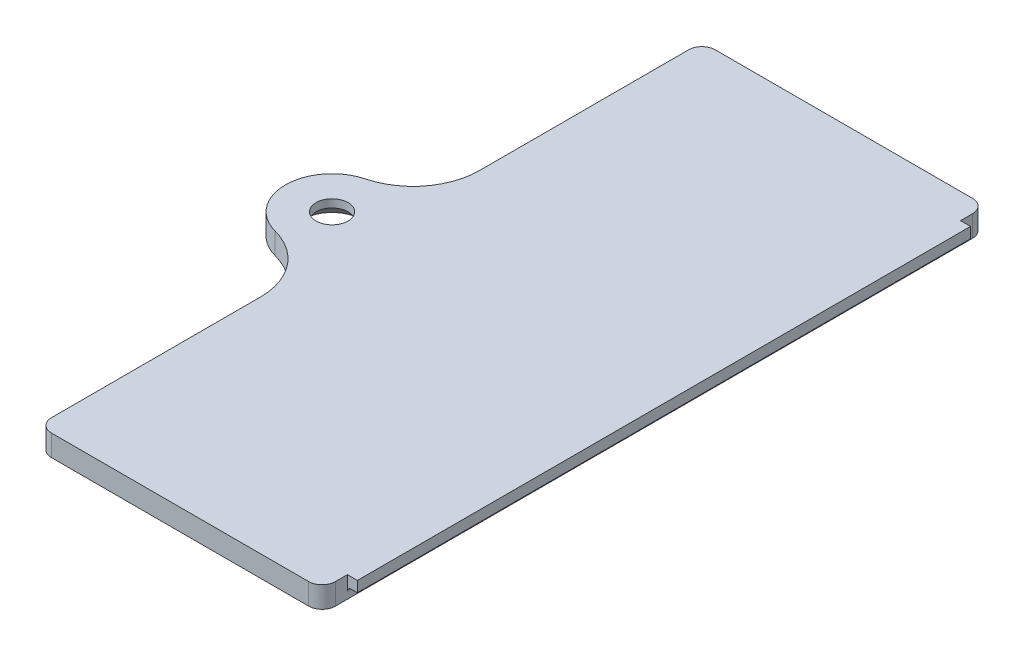
SolidWorks part; units mm, degrees
ref_plane "Front Plane" through (0, 0, 0) normal (0, 0, 1) x (1, 0, 0)
ref_plane "Top Plane" through (0, 0, 0) normal (0, 1, 0) x (1, 0, 0)
ref_plane "Right Plane" through (0, 0, 0) normal (1, 0, 0) x (0, 0, -1)
sketch "Door Plate 1.6 + screw ear (R5 / R3.5) Sketch" plane through (0, 0, 0) normal (0, 1, 0) x (1, 0, 0)
  line L0 (9.35, 15.1) -> (30.65, 15.1)
  line L1 (30.65, 15.1) -> (30.65, 64.9)
  line L2 (30.65, 64.9) -> (9.35, 64.9)
  line L3 (9.35, 64.9) -> (9.35, 48.2236)
  line L4 (9.35, 31.7764) -> (9.35, 15.1)
  arc A0 (9.35, 31.7764) -> (5.6147, 36.6138) centre (4.35, 31.7764) ccw
  arc A1 (5.6147, 36.6138) -> (5.6147, 43.3862) centre (6.5, 40) cw
  arc A2 (5.6147, 43.3862) -> (9.35, 48.2236) centre (4.35, 48.2236) ccw
extrude "Door Plate 1.6 + screw ear (R5 / R3.5)" add sketch "Door Plate 1.6 + screw ear (R5 / R3.5) Sketch" along normal blind 1.6
ref_plane "Hook Flange Plane y0.8" through (0, 0.8, 0) normal (0, 1, 0) x (1, 0, 0)
sketch "Hook Flange 0.75 x 0.8 (inner-face plane) Sketch" plane through (0, 0.8, 0) normal (0, 1, 0) x (1, 0, 0)
  line L0 (30.5, 17) -> (31.4, 17)
  line L1 (31.4, 17) -> (31.4, 63)
  line L2 (31.4, 63) -> (30.5, 63)
  line L3 (30.5, 63) -> (30.5, 17)
extrude "Hook Flange 0.75 x 0.8 (inner-face plane)" add sketch "Hook Flange 0.75 x 0.8 (inner-face plane) Sketch" along normal blind 0.8
sketch "Screw Hole 2.4 (free) Sketch" plane through (0, 0, 0) normal (0, 1, 0) x (1, 0, 0)
  circle A0 centre (6.5, 40) radius 1.2
extrude "Screw Hole 2.4 (free)" cut sketch "Screw Hole 2.4 (free) Sketch" along normal through all
chamfer "Screw CSK 90deg (M2)" distance 1 angle 45 1 edges at (6.5, 0, -38.8)
fillet "Door Corners R1 (print)" radius 1 4 edges at (9.35, 0.8, -64.9) (30.65, 0.8, -64.9) (30.65, 0.8, -15.1) (9.35, 0.8, -15.1)
fillet "Hook Flange Root Fillet R0.3" radius 0.3 1 edges at (30.65, 0.8, -40)
sketch "Door Text Slits 8160749347 + PLEASE RETURN (outer face, 0.84 stroke) Sketch" plane through (0, 0, 0) normal (0, 1, 0) x (1, 0, 0)
  line L0 (27.28, 17.22) -> (21.12, 17.22)
  line L1 (20.6, 17.74) -> (20.6, 20.5)
  line L2 (21.12, 21.02) -> (27.28, 21.02)
  line L3 (27.8, 20.5) -> (27.8, 17.74)
  line L4 (21.12, 17.32) -> (27.28, 17.32)
  line L5 (27.7, 17.74) -> (27.7, 20.5)
  line L6 (27.28, 20.92) -> (21.12, 20.92)
  line L7 (20.7, 20.5) -> (20.7, 17.74)
  line L8 (21.12, 24.28) -> (27.28, 24.28)
  line L9 (27.8, 23.76) -> (27.8, 22.76)
  line L10 (26.76, 22.76) -> (26.76, 23.24)
  line L11 (26.76, 23.24) -> (21.12, 23.24)
  line L12 (27.7, 23.76) -> (27.7, 22.76)
  line L13 (26.86, 22.76) -> (26.86, 23.34)
  line L14 (26.86, 23.34) -> (21.12, 23.34)
  line L15 (21.12, 24.18) -> (27.28, 24.18)
  line L16 (21.12, 30.3) -> (24.2, 30.3)
  line L17 (24.72, 29.78) -> (24.72, 27.54)
  line L18 (24.72, 27.54) -> (26.76, 27.54)
  line L19 (26.76, 27.54) -> (26.76, 29.78)
  line L20 (27.8, 29.78) -> (27.8, 27.02)
  line L21 (27.28, 26.5) -> (21.12, 26.5)
  line L22 (20.6, 27.02) -> (20.6, 29.78)
  line L23 (27.7, 29.78) -> (27.7, 27.02)
  line L24 (27.28, 26.6) -> (21.12, 26.6)
  line L25 (20.7, 27.02) -> (20.7, 29.78)
  line L26 (21.12, 30.2) -> (24.2, 30.2)
  line L27 (24.62, 29.78) -> (24.62, 27.44)
  line L28 (24.62, 27.44) -> (26.86, 27.44)
  line L29 (26.86, 27.44) -> (26.86, 29.78)
  line L30 (27.28, 31.14) -> (21.12, 31.14)
  line L31 (20.6, 31.66) -> (20.6, 34.42)
  line L32 (21.12, 34.94) -> (27.28, 34.94)
  line L33 (27.8, 34.42) -> (27.8, 31.66)
  line L34 (21.12, 31.24) -> (27.28, 31.24)
  line L35 (27.7, 31.66) -> (27.7, 34.42)
  line L36 (27.28, 34.84) -> (21.12, 34.84)
  line L37 (20.7, 34.42) -> (20.7, 31.66)
  line L38 (20.9832, 37.8817) -> (27.1432, 39.5617)
  line L39 (27.8, 39.06) -> (27.8, 36.3)
  line L40 (26.76, 36.3) -> (26.76, 38.3792)
  line L41 (26.76, 38.3792) -> (21.2568, 36.8783)
  line L42 (27.7, 39.06) -> (27.7, 36.3)
  line L43 (26.86, 36.3) -> (26.86, 38.5101)
  line L44 (26.86, 38.5101) -> (21.2305, 36.9748)
  line L45 (21.0095, 37.7852) -> (27.1695, 39.4652)
  line L46 (21.12, 44.22) -> (27.28, 44.22)
  line L47 (27.28, 43.18) -> (24.72, 43.18)
  line L48 (24.72, 43.18) -> (24.72, 41.46)
  line L49 (24.72, 41.46) -> (27.28, 41.46)
  line L50 (27.28, 40.42) -> (24.2, 40.42)
  line L51 (23.68, 40.94) -> (23.68, 43.18)
  line L52 (23.68, 43.18) -> (21.12, 43.18)
  line L53 (27.28, 40.52) -> (24.2, 40.52)
  line L54 (23.78, 40.94) -> (23.78, 43.28)
  line L55 (23.78, 43.28) -> (21.12, 43.28)
  line L56 (21.12, 44.12) -> (27.28, 44.12)
  line L57 (27.28, 43.28) -> (24.62, 43.28)
  line L58 (24.62, 43.28) -> (24.62, 41.36)
  line L59 (24.62, 41.36) -> (27.28, 41.36)
  line L60 (23.68, 47.82) -> (21.64, 47.82)
  line L61 (21.64, 47.82) -> (21.64, 45.58)
  line L62 (20.6, 45.58) -> (20.6, 48.34)
  line L63 (21.12, 48.86) -> (27.28, 48.86)
  line L64 (27.8, 48.34) -> (27.8, 45.58)
  line L65 (27.28, 45.06) -> (24.2, 45.06)
  line L66 (23.68, 45.58) -> (23.68, 47.82)
  line L67 (20.7, 48.34) -> (20.7, 45.58)
  line L68 (21.54, 45.58) -> (21.54, 47.92)
  line L69 (21.54, 47.92) -> (23.78, 47.92)
  line L70 (23.78, 47.92) -> (23.78, 45.58)
  line L71 (24.2, 45.16) -> (27.28, 45.16)
  line L72 (27.7, 45.58) -> (27.7, 48.34)
  line L73 (27.28, 48.76) -> (21.12, 48.76)
  line L74 (21.64, 52.46) -> (21.64, 50.22)
  line L75 (20.6, 50.22) -> (20.6, 52.98)
  line L76 (21.12, 53.5) -> (27.28, 53.5)
  line L77 (27.8, 52.98) -> (27.8, 50.22)
  line L78 (26.76, 50.22) -> (26.76, 52.46)
  line L79 (26.76, 52.46) -> (24.72, 52.46)
  line L80 (24.72, 52.46) -> (24.72, 51.02)
  line L81 (23.68, 51.02) -> (23.68, 52.46)
  line L82 (23.68, 52.46) -> (21.64, 52.46)
  line L83 (27.28, 53.4) -> (21.12, 53.4)
  line L84 (20.7, 52.98) -> (20.7, 50.22)
  line L85 (21.54, 50.22) -> (21.54, 52.56)
  line L86 (21.54, 52.56) -> (23.78, 52.56)
  line L87 (23.78, 52.56) -> (23.78, 51.02)
  line L88 (24.62, 51.02) -> (24.62, 52.56)
  line L89 (24.62, 52.56) -> (26.86, 52.56)
  line L90 (26.86, 52.56) -> (26.86, 50.22)
  line L91 (27.7, 50.22) -> (27.7, 52.98)
  line L92 (21.12, 58.14) -> (27.28, 58.14)
  line L93 (27.28, 57.1) -> (24.72, 57.1)
  line L94 (24.72, 57.1) -> (24.72, 55.38)
  line L95 (24.72, 55.38) -> (27.28, 55.38)
  line L96 (27.28, 54.34) -> (24.2, 54.34)
  line L97 (23.68, 54.86) -> (23.68, 57.1)
  line L98 (23.68, 57.1) -> (21.12, 57.1)
  line L99 (27.28, 54.44) -> (24.2, 54.44)
  line L100 (23.78, 54.86) -> (23.78, 57.2)
  line L101 (23.78, 57.2) -> (21.12, 57.2)
  line L102 (21.12, 58.04) -> (27.28, 58.04)
  line L103 (27.28, 57.2) -> (24.62, 57.2)
  line L104 (24.62, 57.2) -> (24.62, 55.28)
  line L105 (24.62, 55.28) -> (27.28, 55.28)
  line L106 (20.9832, 61.0817) -> (27.1432, 62.7617)
  line L107 (27.8, 62.26) -> (27.8, 59.5)
  line L108 (26.76, 59.5) -> (26.76, 61.5792)
  line L109 (26.76, 61.5792) -> (21.2568, 60.0783)
  line L110 (27.7, 62.26) -> (27.7, 59.5)
  line L111 (26.86, 59.5) -> (26.86, 61.7101)
  line L112 (26.86, 61.7101) -> (21.2305, 60.1748)
  line L113 (21.0095, 60.9852) -> (27.1695, 62.6652)
  line L114 (18.28, 19.76) -> (16.2, 19.76)
  line L115 (15.68, 19.24) -> (15.68, 17.8)
  line L116 (15.68, 17.8) -> (14.12, 17.8)
  line L117 (14.12, 16.76) -> (18.28, 16.76)
  line L118 (18.8, 17.28) -> (18.8, 19.24)
  line L119 (14.12, 16.86) -> (18.28, 16.86)
  line L120 (18.7, 17.28) -> (18.7, 19.24)
  line L121 (18.28, 19.66) -> (16.2, 19.66)
  line L122 (15.78, 19.24) -> (15.78, 17.7)
  line L123 (15.78, 17.7) -> (14.12, 17.7)
  line L124 (13.6, 21.12) -> (13.6, 22.48)
  line L125 (14.64, 22.48) -> (14.64, 21.64)
  line L126 (14.64, 21.64) -> (18.28, 21.64)
  line L127 (18.28, 20.6) -> (14.12, 20.6)
  line L128 (14.54, 21.54) -> (18.28, 21.54)
  line L129 (18.28, 20.7) -> (14.12, 20.7)
  line L130 (13.7, 21.12) -> (13.7, 22.48)
  line L131 (14.54, 22.48) -> (14.54, 21.54)
  line L132 (14.64, 25.72) -> (14.64, 24.88)
  line L133 (14.64, 24.88) -> (15.68, 24.88)
  line L134 (15.68, 24.88) -> (15.68, 25.42)
  line L135 (16.72, 25.42) -> (16.72, 24.88)
  line L136 (16.72, 24.88) -> (17.76, 24.88)
  line L137 (17.76, 24.88) -> (17.76, 25.72)
  line L138 (18.8, 25.72) -> (18.8, 24.36)
  line L139 (18.28, 23.84) -> (14.12, 23.84)
  line L140 (13.6, 24.36) -> (13.6, 25.72)
  line L141 (18.7, 25.72) -> (18.7, 24.36)
  line L142 (18.28, 23.94) -> (14.12, 23.94)
  line L143 (13.7, 24.36) -> (13.7, 25.72)
  line L144 (14.54, 25.72) -> (14.54, 24.78)
  line L145 (14.54, 24.78) -> (15.78, 24.78)
  line L146 (15.78, 24.78) -> (15.78, 25.42)
  line L147 (16.62, 25.42) -> (16.62, 24.78)
  line L148 (16.62, 24.78) -> (17.86, 24.78)
  line L149 (17.86, 24.78) -> (17.86, 25.72)
  line L150 (14.12, 29.04) -> (15.68, 29.04)
  line L151 (15.68, 29.04) -> (15.68, 28.12)
  line L152 (15.68, 28.12) -> (14.12, 28.12)
  line L153 (14.12, 27.08) -> (18.28, 27.08)
  line L154 (18.8, 27.6) -> (18.8, 29.56)
  line L155 (18.28, 30.08) -> (14.12, 30.08)
  line L156 (14.12, 27.18) -> (18.28, 27.18)
  line L157 (18.7, 27.6) -> (18.7, 29.56)
  line L158 (18.28, 29.98) -> (14.12, 29.98)
  line L159 (14.12, 29.14) -> (15.78, 29.14)
  line L160 (15.78, 29.14) -> (15.78, 28.02)
  line L161 (15.78, 28.02) -> (14.12, 28.02)
  line L162 (13.6, 31.44) -> (13.6, 33.2)
  line L163 (14.12, 33.72) -> (16.2, 33.72)
  line L164 (16.72, 33.2) -> (16.72, 31.96)
  line L165 (16.72, 31.96) -> (17.76, 31.96)
  line L166 (17.76, 31.96) -> (17.76, 33.2)
  line L167 (18.8, 33.2) -> (18.8, 31.44)
  line L168 (18.28, 30.92) -> (16.2, 30.92)
  line L169 (15.68, 31.44) -> (15.68, 32.68)
  line L170 (15.68, 32.68) -> (14.64, 32.68)
  line L171 (14.64, 32.68) -> (14.64, 31.44)
  line L172 (17.86, 31.86) -> (17.86, 33.2)
  line L173 (18.7, 33.2) -> (18.7, 31.44)
  line L174 (18.28, 31.02) -> (16.2, 31.02)
  line L175 (15.78, 31.44) -> (15.78, 32.78)
  line L176 (15.78, 32.78) -> (14.54, 32.78)
  line L177 (14.54, 32.78) -> (14.54, 31.44)
  line L178 (13.7, 31.44) -> (13.7, 33.2)
  line L179 (14.12, 33.62) -> (16.2, 33.62)
  line L180 (16.62, 33.2) -> (16.62, 31.86)
  line L181 (16.62, 31.86) -> (17.86, 31.86)
  line L182 (14.64, 36.44) -> (14.64, 35.6)
  line L183 (14.64, 35.6) -> (15.68, 35.6)
  line L184 (15.68, 35.6) -> (15.68, 36.14)
  line L185 (16.72, 36.14) -> (16.72, 35.6)
  line L186 (16.72, 35.6) -> (17.76, 35.6)
  line L187 (17.76, 35.6) -> (17.76, 36.44)
  line L188 (18.8, 36.44) -> (18.8, 35.08)
  line L189 (18.28, 34.56) -> (14.12, 34.56)
  line L190 (13.6, 35.08) -> (13.6, 36.44)
  line L191 (18.7, 36.44) -> (18.7, 35.08)
  line L192 (18.28, 34.66) -> (14.12, 34.66)
  line L193 (13.7, 35.08) -> (13.7, 36.44)
  line L194 (14.54, 36.44) -> (14.54, 35.5)
  line L195 (14.54, 35.5) -> (15.78, 35.5)
  line L196 (15.78, 35.5) -> (15.78, 36.14)
  line L197 (16.62, 36.14) -> (16.62, 35.5)
  line L198 (16.62, 35.5) -> (17.86, 35.5)
  line L199 (17.86, 35.5) -> (17.86, 36.44)
  line L200 (15.68, 43.52) -> (15.68, 43.4246)
  line L201 (15.68, 43.4246) -> (14.3226, 43.9989)
  line L202 (13.9174, 43.0411) -> (15.68, 42.2954)
  line L203 (15.68, 42.2954) -> (15.68, 41.28)
  line L204 (15.68, 41.28) -> (14.12, 41.28)
  line L205 (14.12, 40.24) -> (18.28, 40.24)
  line L206 (18.8, 40.76) -> (18.8, 43.52)
  line L207 (18.28, 44.04) -> (16.2, 44.04)
  line L208 (14.12, 40.34) -> (18.28, 40.34)
  line L209 (18.7, 40.76) -> (18.7, 43.52)
  line L210 (18.28, 43.94) -> (16.2, 43.94)
  line L211 (15.78, 43.52) -> (15.78, 43.2737)
  line L212 (15.78, 43.2737) -> (14.2836, 43.9068)
  line L213 (13.9564, 43.1332) -> (15.78, 42.3617)
  line L214 (15.78, 42.3617) -> (15.78, 41.18)
  line L215 (15.78, 41.18) -> (14.12, 41.18)
  line L216 (14.64, 46.76) -> (14.64, 45.92)
  line L217 (14.64, 45.92) -> (15.68, 45.92)
  line L218 (15.68, 45.92) -> (15.68, 46.46)
  line L219 (16.72, 46.46) -> (16.72, 45.92)
  line L220 (16.72, 45.92) -> (17.76, 45.92)
  line L221 (17.76, 45.92) -> (17.76, 46.76)
  line L222 (18.8, 46.76) -> (18.8, 45.4)
  line L223 (18.28, 44.88) -> (14.12, 44.88)
  line L224 (13.6, 45.4) -> (13.6, 46.76)
  line L225 (18.7, 46.76) -> (18.7, 45.4)
  line L226 (18.28, 44.98) -> (14.12, 44.98)
  line L227 (13.7, 45.4) -> (13.7, 46.76)
  line L228 (14.54, 46.76) -> (14.54, 45.82)
  line L229 (14.54, 45.82) -> (15.78, 45.82)
  line L230 (15.78, 45.82) -> (15.78, 46.46)
  line L231 (16.62, 46.46) -> (16.62, 45.82)
  line L232 (16.62, 45.82) -> (17.86, 45.82)
  line L233 (17.86, 45.82) -> (17.86, 46.76)
  line L234 (14.12, 49) -> (17.76, 49)
  line L235 (17.76, 49) -> (17.76, 48.64)
  line L236 (18.8, 48.64) -> (18.8, 50.4)
  line L237 (17.76, 50.4) -> (17.76, 50.04)
  line L238 (17.76, 50.04) -> (14.12, 50.04)
  line L239 (18.7, 48.64) -> (18.7, 50.4)
  line L240 (17.86, 50.4) -> (17.86, 49.94)
  line L241 (17.86, 49.94) -> (14.12, 49.94)
  line L242 (14.12, 49.1) -> (17.86, 49.1)
  line L243 (17.86, 49.1) -> (17.86, 48.64)
  line L244 (14.12, 54.76) -> (18.28, 54.76)
  line L245 (18.28, 53.72) -> (14.64, 53.72)
  line L246 (14.64, 53.72) -> (14.64, 52.8)
  line L247 (14.64, 52.8) -> (18.28, 52.8)
  line L248 (18.28, 51.76) -> (14.12, 51.76)
  line L249 (13.6, 52.28) -> (13.6, 54.24)
  line L250 (14.54, 52.7) -> (18.28, 52.7)
  line L251 (18.28, 51.86) -> (14.12, 51.86)
  line L252 (13.7, 52.28) -> (13.7, 54.24)
  line L253 (14.12, 54.66) -> (18.28, 54.66)
  line L254 (18.28, 53.82) -> (14.54, 53.82)
  line L255 (14.54, 53.82) -> (14.54, 52.7)
  line L256 (15.68, 58.88) -> (15.68, 58.7846)
  line L257 (15.68, 58.7846) -> (14.3226, 59.3589)
  line L258 (13.9174, 58.4011) -> (15.68, 57.6554)
  line L259 (15.68, 57.6554) -> (15.68, 56.64)
  line L260 (15.68, 56.64) -> (14.12, 56.64)
  line L261 (14.12, 55.6) -> (18.28, 55.6)
  line L262 (18.8, 56.12) -> (18.8, 58.88)
  line L263 (18.28, 59.4) -> (16.2, 59.4)
  line L264 (14.12, 55.7) -> (18.28, 55.7)
  line L265 (18.7, 56.12) -> (18.7, 58.88)
  line L266 (18.28, 59.3) -> (16.2, 59.3)
  line L267 (15.78, 58.88) -> (15.78, 58.6337)
  line L268 (15.78, 58.6337) -> (14.2836, 59.2668)
  line L269 (13.9564, 58.4932) -> (15.78, 57.7217)
  line L270 (15.78, 57.7217) -> (15.78, 56.54)
  line L271 (15.78, 56.54) -> (14.12, 56.54)
  line L272 (14.12, 63.24) -> (18.28, 63.24)
  line L273 (18.8, 62.72) -> (18.8, 60.76)
  line L274 (18.28, 60.24) -> (14.12, 60.24)
  line L275 (14.12, 61.28) -> (17.76, 61.28)
  line L276 (17.76, 61.28) -> (17.76, 62.2)
  line L277 (17.76, 62.2) -> (14.12, 62.2)
  line L278 (18.28, 60.34) -> (14.12, 60.34)
  line L279 (14.12, 61.18) -> (17.86, 61.18)
  line L280 (17.86, 61.18) -> (17.86, 62.3)
  line L281 (17.86, 62.3) -> (14.12, 62.3)
  line L282 (14.12, 63.14) -> (18.28, 63.14)
  line L283 (18.7, 62.72) -> (18.7, 60.76)
  arc A0 (27.8, 17.74) -> (27.28, 17.22) centre (27.28, 17.74) cw
  arc A1 (21.12, 17.22) -> (20.6, 17.74) centre (21.12, 17.74) cw
  arc A2 (20.6, 20.5) -> (21.12, 21.02) centre (21.12, 20.5) cw
  arc A3 (27.28, 21.02) -> (27.8, 20.5) centre (27.28, 20.5) cw
  arc A4 (20.7, 17.74) -> (21.12, 17.32) centre (21.12, 17.74) ccw
  arc A5 (27.28, 17.32) -> (27.7, 17.74) centre (27.28, 17.74) ccw
  arc A6 (27.7, 20.5) -> (27.28, 20.92) centre (27.28, 20.5) ccw
  arc A7 (21.12, 20.92) -> (20.7, 20.5) centre (21.12, 20.5) ccw
  arc A8 (21.12, 23.24) -> (21.12, 24.28) centre (21.12, 23.76) cw
  arc A9 (27.28, 24.28) -> (27.8, 23.76) centre (27.28, 23.76) cw
  arc A10 (27.8, 22.76) -> (26.76, 22.76) centre (27.28, 22.76) cw
  arc A11 (27.7, 22.76) -> (26.86, 22.76) centre (27.28, 22.76) cw
  arc A12 (21.12, 23.34) -> (21.12, 24.18) centre (21.12, 23.76) cw
  arc A13 (27.28, 24.18) -> (27.7, 23.76) centre (27.28, 23.76) cw
  arc A14 (20.6, 29.78) -> (21.12, 30.3) centre (21.12, 29.78) cw
  arc A15 (24.2, 30.3) -> (24.72, 29.78) centre (24.2, 29.78) cw
  arc A16 (26.76, 29.78) -> (27.8, 29.78) centre (27.28, 29.78) cw
  arc A17 (27.8, 27.02) -> (27.28, 26.5) centre (27.28, 27.02) cw
  arc A18 (21.12, 26.5) -> (20.6, 27.02) centre (21.12, 27.02) cw
  arc A19 (26.86, 29.78) -> (27.7, 29.78) centre (27.28, 29.78) cw
  arc A20 (27.7, 27.02) -> (27.28, 26.6) centre (27.28, 27.02) cw
  arc A21 (21.12, 26.6) -> (20.7, 27.02) centre (21.12, 27.02) cw
  arc A22 (20.7, 29.78) -> (21.12, 30.2) centre (21.12, 29.78) cw
  arc A23 (24.2, 30.2) -> (24.62, 29.78) centre (24.2, 29.78) cw
  arc A24 (27.8, 31.66) -> (27.28, 31.14) centre (27.28, 31.66) cw
  arc A25 (21.12, 31.14) -> (20.6, 31.66) centre (21.12, 31.66) cw
  arc A26 (20.6, 34.42) -> (21.12, 34.94) centre (21.12, 34.42) cw
  arc A27 (27.28, 34.94) -> (27.8, 34.42) centre (27.28, 34.42) cw
  arc A28 (20.7, 31.66) -> (21.12, 31.24) centre (21.12, 31.66) ccw
  arc A29 (27.28, 31.24) -> (27.7, 31.66) centre (27.28, 31.66) ccw
  arc A30 (27.7, 34.42) -> (27.28, 34.84) centre (27.28, 34.42) ccw
  arc A31 (21.12, 34.84) -> (20.7, 34.42) centre (21.12, 34.42) ccw
  arc A32 (21.2568, 36.8783) -> (20.9832, 37.8817) centre (21.12, 37.38) cw
  arc A33 (27.1432, 39.5617) -> (27.8, 39.06) centre (27.28, 39.06) cw
  arc A34 (27.8, 36.3) -> (26.76, 36.3) centre (27.28, 36.3) cw
  arc A35 (27.7, 36.3) -> (26.86, 36.3) centre (27.28, 36.3) cw
  arc A36 (21.2305, 36.9748) -> (21.0095, 37.7852) centre (21.12, 37.38) cw
  arc A37 (27.1695, 39.4652) -> (27.7, 39.06) centre (27.28, 39.06) cw
  arc A38 (21.12, 43.18) -> (21.12, 44.22) centre (21.12, 43.7) cw
  arc A39 (27.28, 44.22) -> (27.8, 43.7) centre (27.28, 43.7) cw
  arc A40 (27.8, 43.7) -> (27.28, 43.18) centre (27.28, 43.7) cw
  arc A41 (27.28, 41.46) -> (27.8, 40.94) centre (27.28, 40.94) cw
  arc A42 (27.8, 40.94) -> (27.28, 40.42) centre (27.28, 40.94) cw
  arc A43 (24.2, 40.42) -> (23.68, 40.94) centre (24.2, 40.94) cw
  arc A44 (27.28, 41.36) -> (27.7, 40.94) centre (27.28, 40.94) cw
  arc A45 (27.7, 40.94) -> (27.28, 40.52) centre (27.28, 40.94) cw
  arc A46 (24.2, 40.52) -> (23.78, 40.94) centre (24.2, 40.94) cw
  arc A47 (21.12, 43.28) -> (21.12, 44.12) centre (21.12, 43.7) cw
  arc A48 (27.28, 44.12) -> (27.7, 43.7) centre (27.28, 43.7) cw
  arc A49 (27.7, 43.7) -> (27.28, 43.28) centre (27.28, 43.7) cw
  arc A50 (21.64, 45.58) -> (20.6, 45.58) centre (21.12, 45.58) cw
  arc A51 (20.6, 48.34) -> (21.12, 48.86) centre (21.12, 48.34) cw
  arc A52 (27.28, 48.86) -> (27.8, 48.34) centre (27.28, 48.34) cw
  arc A53 (27.8, 45.58) -> (27.28, 45.06) centre (27.28, 45.58) cw
  arc A54 (24.2, 45.06) -> (23.68, 45.58) centre (24.2, 45.58) cw
  arc A55 (21.12, 48.76) -> (20.7, 48.34) centre (21.12, 48.34) ccw
  arc A56 (20.7, 45.58) -> (21.54, 45.58) centre (21.12, 45.58) ccw
  arc A57 (23.78, 45.58) -> (24.2, 45.16) centre (24.2, 45.58) ccw
  arc A58 (27.28, 45.16) -> (27.7, 45.58) centre (27.28, 45.58) ccw
  arc A59 (27.7, 48.34) -> (27.28, 48.76) centre (27.28, 48.34) ccw
  arc A60 (21.64, 50.22) -> (20.6, 50.22) centre (21.12, 50.22) cw
  arc A61 (20.6, 52.98) -> (21.12, 53.5) centre (21.12, 52.98) cw
  arc A62 (27.28, 53.5) -> (27.8, 52.98) centre (27.28, 52.98) cw
  arc A63 (27.8, 50.22) -> (26.76, 50.22) centre (27.28, 50.22) cw
  arc A64 (24.72, 51.02) -> (23.68, 51.02) centre (24.2, 51.02) cw
  arc A65 (27.7, 52.98) -> (27.28, 53.4) centre (27.28, 52.98) ccw
  arc A66 (21.12, 53.4) -> (20.7, 52.98) centre (21.12, 52.98) ccw
  arc A67 (20.7, 50.22) -> (21.54, 50.22) centre (21.12, 50.22) ccw
  arc A68 (23.78, 51.02) -> (24.62, 51.02) centre (24.2, 51.02) ccw
  arc A69 (26.86, 50.22) -> (27.7, 50.22) centre (27.28, 50.22) ccw
  arc A70 (21.12, 57.1) -> (21.12, 58.14) centre (21.12, 57.62) cw
  arc A71 (27.28, 58.14) -> (27.8, 57.62) centre (27.28, 57.62) cw
  arc A72 (27.8, 57.62) -> (27.28, 57.1) centre (27.28, 57.62) cw
  arc A73 (27.28, 55.38) -> (27.8, 54.86) centre (27.28, 54.86) cw
  arc A74 (27.8, 54.86) -> (27.28, 54.34) centre (27.28, 54.86) cw
  arc A75 (24.2, 54.34) -> (23.68, 54.86) centre (24.2, 54.86) cw
  arc A76 (27.28, 55.28) -> (27.7, 54.86) centre (27.28, 54.86) cw
  arc A77 (27.7, 54.86) -> (27.28, 54.44) centre (27.28, 54.86) cw
  arc A78 (24.2, 54.44) -> (23.78, 54.86) centre (24.2, 54.86) cw
  arc A79 (21.12, 57.2) -> (21.12, 58.04) centre (21.12, 57.62) cw
  arc A80 (27.28, 58.04) -> (27.7, 57.62) centre (27.28, 57.62) cw
  arc A81 (27.7, 57.62) -> (27.28, 57.2) centre (27.28, 57.62) cw
  arc A82 (21.2568, 60.0783) -> (20.9832, 61.0817) centre (21.12, 60.58) cw
  arc A83 (27.1432, 62.7617) -> (27.8, 62.26) centre (27.28, 62.26) cw
  arc A84 (27.8, 59.5) -> (26.76, 59.5) centre (27.28, 59.5) cw
  arc A85 (27.7, 59.5) -> (26.86, 59.5) centre (27.28, 59.5) cw
  arc A86 (21.2305, 60.1748) -> (21.0095, 60.9852) centre (21.12, 60.58) cw
  arc A87 (27.1695, 62.6652) -> (27.7, 62.26) centre (27.28, 62.26) cw
  arc A88 (16.2, 19.76) -> (15.68, 19.24) centre (16.2, 19.24) ccw
  arc A89 (14.12, 17.8) -> (14.12, 16.76) centre (14.12, 17.28) ccw
  arc A90 (18.28, 16.76) -> (18.8, 17.28) centre (18.28, 17.28) ccw
  arc A91 (18.8, 19.24) -> (18.28, 19.76) centre (18.28, 19.24) ccw
  arc A92 (14.12, 17.7) -> (14.12, 16.86) centre (14.12, 17.28) ccw
  arc A93 (18.28, 16.86) -> (18.7, 17.28) centre (18.28, 17.28) ccw
  arc A94 (18.7, 19.24) -> (18.28, 19.66) centre (18.28, 19.24) ccw
  arc A95 (16.2, 19.66) -> (15.78, 19.24) centre (16.2, 19.24) ccw
  arc A96 (13.6, 22.48) -> (14.64, 22.48) centre (14.12, 22.48) cw
  arc A97 (18.28, 21.64) -> (18.8, 21.12) centre (18.28, 21.12) cw
  arc A98 (18.8, 21.12) -> (18.28, 20.6) centre (18.28, 21.12) cw
  arc A99 (14.12, 20.6) -> (13.6, 21.12) centre (14.12, 21.12) cw
  arc A100 (18.28, 21.54) -> (18.7, 21.12) centre (18.28, 21.12) cw
  arc A101 (18.7, 21.12) -> (18.28, 20.7) centre (18.28, 21.12) cw
  arc A102 (14.12, 20.7) -> (13.7, 21.12) centre (14.12, 21.12) cw
  arc A103 (13.7, 22.48) -> (14.54, 22.48) centre (14.12, 22.48) cw
  arc A104 (15.68, 25.42) -> (16.72, 25.42) centre (16.2, 25.42) cw
  arc A105 (17.76, 25.72) -> (18.8, 25.72) centre (18.28, 25.72) cw
  arc A106 (18.8, 24.36) -> (18.28, 23.84) centre (18.28, 24.36) cw
  arc A107 (14.12, 23.84) -> (13.6, 24.36) centre (14.12, 24.36) cw
  arc A108 (13.6, 25.72) -> (14.64, 25.72) centre (14.12, 25.72) cw
  arc A109 (17.86, 25.72) -> (18.7, 25.72) centre (18.28, 25.72) cw
  arc A110 (18.7, 24.36) -> (18.28, 23.94) centre (18.28, 24.36) cw
  arc A111 (14.12, 23.94) -> (13.7, 24.36) centre (14.12, 24.36) cw
  arc A112 (13.7, 25.72) -> (14.54, 25.72) centre (14.12, 25.72) cw
  arc A113 (15.78, 25.42) -> (16.62, 25.42) centre (16.2, 25.42) cw
  arc A114 (14.12, 30.08) -> (14.12, 29.04) centre (14.12, 29.56) ccw
  arc A115 (14.12, 28.12) -> (14.12, 27.08) centre (14.12, 27.6) ccw
  arc A116 (18.28, 27.08) -> (18.8, 27.6) centre (18.28, 27.6) ccw
  arc A117 (18.8, 29.56) -> (18.28, 30.08) centre (18.28, 29.56) ccw
  arc A118 (14.12, 28.02) -> (14.12, 27.18) centre (14.12, 27.6) ccw
  arc A119 (18.28, 27.18) -> (18.7, 27.6) centre (18.28, 27.6) ccw
  arc A120 (18.7, 29.56) -> (18.28, 29.98) centre (18.28, 29.56) ccw
  arc A121 (14.12, 29.98) -> (14.12, 29.14) centre (14.12, 29.56) ccw
  arc A122 (14.64, 31.44) -> (13.6, 31.44) centre (14.12, 31.44) cw
  arc A123 (13.6, 33.2) -> (14.12, 33.72) centre (14.12, 33.2) cw
  arc A124 (16.2, 33.72) -> (16.72, 33.2) centre (16.2, 33.2) cw
  arc A125 (17.76, 33.2) -> (18.8, 33.2) centre (18.28, 33.2) cw
  arc A126 (18.8, 31.44) -> (18.28, 30.92) centre (18.28, 31.44) cw
  arc A127 (16.2, 30.92) -> (15.68, 31.44) centre (16.2, 31.44) cw
  arc A128 (17.86, 33.2) -> (18.7, 33.2) centre (18.28, 33.2) cw
  arc A129 (18.7, 31.44) -> (18.28, 31.02) centre (18.28, 31.44) cw
  arc A130 (16.2, 31.02) -> (15.78, 31.44) centre (16.2, 31.44) cw
  arc A131 (14.54, 31.44) -> (13.7, 31.44) centre (14.12, 31.44) cw
  arc A132 (13.7, 33.2) -> (14.12, 33.62) centre (14.12, 33.2) cw
  arc A133 (16.2, 33.62) -> (16.62, 33.2) centre (16.2, 33.2) cw
  arc A134 (15.68, 36.14) -> (16.72, 36.14) centre (16.2, 36.14) cw
  arc A135 (17.76, 36.44) -> (18.8, 36.44) centre (18.28, 36.44) cw
  arc A136 (18.8, 35.08) -> (18.28, 34.56) centre (18.28, 35.08) cw
  arc A137 (14.12, 34.56) -> (13.6, 35.08) centre (14.12, 35.08) cw
  arc A138 (13.6, 36.44) -> (14.64, 36.44) centre (14.12, 36.44) cw
  arc A139 (17.86, 36.44) -> (18.7, 36.44) centre (18.28, 36.44) cw
  arc A140 (18.7, 35.08) -> (18.28, 34.66) centre (18.28, 35.08) cw
  arc A141 (14.12, 34.66) -> (13.7, 35.08) centre (14.12, 35.08) cw
  arc A142 (13.7, 36.44) -> (14.54, 36.44) centre (14.12, 36.44) cw
  arc A143 (15.78, 36.14) -> (16.62, 36.14) centre (16.2, 36.14) cw
  arc A144 (14.3226, 43.9989) -> (13.9174, 43.0411) centre (14.12, 43.52) ccw
  arc A145 (14.12, 41.28) -> (14.12, 40.24) centre (14.12, 40.76) ccw
  arc A146 (18.28, 40.24) -> (18.8, 40.76) centre (18.28, 40.76) ccw
  arc A147 (18.8, 43.52) -> (18.28, 44.04) centre (18.28, 43.52) ccw
  arc A148 (16.2, 44.04) -> (15.68, 43.52) centre (16.2, 43.52) ccw
  arc A149 (14.12, 41.18) -> (14.12, 40.34) centre (14.12, 40.76) ccw
  arc A150 (18.28, 40.34) -> (18.7, 40.76) centre (18.28, 40.76) ccw
  arc A151 (18.7, 43.52) -> (18.28, 43.94) centre (18.28, 43.52) ccw
  arc A152 (16.2, 43.94) -> (15.78, 43.52) centre (16.2, 43.52) ccw
  arc A153 (14.2836, 43.9068) -> (13.9564, 43.1332) centre (14.12, 43.52) ccw
  arc A154 (15.68, 46.46) -> (16.72, 46.46) centre (16.2, 46.46) cw
  arc A155 (17.76, 46.76) -> (18.8, 46.76) centre (18.28, 46.76) cw
  arc A156 (18.8, 45.4) -> (18.28, 44.88) centre (18.28, 45.4) cw
  arc A157 (14.12, 44.88) -> (13.6, 45.4) centre (14.12, 45.4) cw
  arc A158 (13.6, 46.76) -> (14.64, 46.76) centre (14.12, 46.76) cw
  arc A159 (17.86, 46.76) -> (18.7, 46.76) centre (18.28, 46.76) cw
  arc A160 (18.7, 45.4) -> (18.28, 44.98) centre (18.28, 45.4) cw
  arc A161 (14.12, 44.98) -> (13.7, 45.4) centre (14.12, 45.4) cw
  arc A162 (13.7, 46.76) -> (14.54, 46.76) centre (14.12, 46.76) cw
  arc A163 (15.78, 46.46) -> (16.62, 46.46) centre (16.2, 46.46) cw
  arc A164 (14.12, 50.04) -> (14.12, 49) centre (14.12, 49.52) ccw
  arc A165 (17.76, 48.64) -> (18.8, 48.64) centre (18.28, 48.64) ccw
  arc A166 (18.8, 50.4) -> (17.76, 50.4) centre (18.28, 50.4) ccw
  arc A167 (17.86, 48.64) -> (18.7, 48.64) centre (18.28, 48.64) ccw
  arc A168 (18.7, 50.4) -> (17.86, 50.4) centre (18.28, 50.4) ccw
  arc A169 (14.12, 49.94) -> (14.12, 49.1) centre (14.12, 49.52) ccw
  arc A170 (18.28, 54.76) -> (18.8, 54.24) centre (18.28, 54.24) cw
  arc A171 (18.8, 54.24) -> (18.28, 53.72) centre (18.28, 54.24) cw
  arc A172 (18.28, 52.8) -> (18.8, 52.28) centre (18.28, 52.28) cw
  arc A173 (18.8, 52.28) -> (18.28, 51.76) centre (18.28, 52.28) cw
  arc A174 (14.12, 51.76) -> (13.6, 52.28) centre (14.12, 52.28) cw
  arc A175 (13.6, 54.24) -> (14.12, 54.76) centre (14.12, 54.24) cw
  arc A176 (18.28, 52.7) -> (18.7, 52.28) centre (18.28, 52.28) cw
  arc A177 (18.7, 52.28) -> (18.28, 51.86) centre (18.28, 52.28) cw
  arc A178 (14.12, 51.86) -> (13.7, 52.28) centre (14.12, 52.28) cw
  arc A179 (13.7, 54.24) -> (14.12, 54.66) centre (14.12, 54.24) cw
  arc A180 (18.28, 54.66) -> (18.7, 54.24) centre (18.28, 54.24) cw
  arc A181 (18.7, 54.24) -> (18.28, 53.82) centre (18.28, 54.24) cw
  arc A182 (14.3226, 59.3589) -> (13.9174, 58.4011) centre (14.12, 58.88) ccw
  arc A183 (14.12, 56.64) -> (14.12, 55.6) centre (14.12, 56.12) ccw
  arc A184 (18.28, 55.6) -> (18.8, 56.12) centre (18.28, 56.12) ccw
  arc A185 (18.8, 58.88) -> (18.28, 59.4) centre (18.28, 58.88) ccw
  arc A186 (16.2, 59.4) -> (15.68, 58.88) centre (16.2, 58.88) ccw
  arc A187 (14.12, 56.54) -> (14.12, 55.7) centre (14.12, 56.12) ccw
  arc A188 (18.28, 55.7) -> (18.7, 56.12) centre (18.28, 56.12) ccw
  arc A189 (18.7, 58.88) -> (18.28, 59.3) centre (18.28, 58.88) ccw
  arc A190 (16.2, 59.3) -> (15.78, 58.88) centre (16.2, 58.88) ccw
  arc A191 (14.2836, 59.2668) -> (13.9564, 58.4932) centre (14.12, 58.88) ccw
  arc A192 (18.28, 63.24) -> (18.8, 62.72) centre (18.28, 62.72) cw
  arc A193 (18.8, 60.76) -> (18.28, 60.24) centre (18.28, 60.76) cw
  arc A194 (14.12, 60.24) -> (14.12, 61.28) centre (14.12, 60.76) cw
  arc A195 (14.12, 62.2) -> (14.12, 63.24) centre (14.12, 62.72) cw
  arc A196 (14.12, 60.34) -> (14.12, 61.18) centre (14.12, 60.76) cw
  arc A197 (14.12, 62.3) -> (14.12, 63.14) centre (14.12, 62.72) cw
  arc A198 (18.28, 63.14) -> (18.7, 62.72) centre (18.28, 62.72) cw
  arc A199 (18.7, 60.76) -> (18.28, 60.34) centre (18.28, 60.76) cw
extrude "Door Text Slits 8160749347 + PLEASE RETURN (outer face, 0.84 stroke)" cut sketch "Door Text Slits 8160749347 + PLEASE RETURN (outer face, 0.84 stroke) Sketch" along normal blind 0.4
sketch "Door Text Counter Slits (outer face) Sketch" plane through (0, 0, 0) normal (0, 1, 0) x (1, 0, 0)
  line L0 (26.86, 18.16) -> (26.86, 20.08)
  line L1 (26.86, 20.08) -> (24.62, 20.08)
  line L2 (24.62, 20.08) -> (24.62, 18.16)
  line L3 (24.62, 18.16) -> (26.86, 18.16)
  line L4 (24.72, 19.98) -> (24.72, 18.26)
  line L5 (24.72, 18.26) -> (26.76, 18.26)
  line L6 (26.76, 18.26) -> (26.76, 19.98)
  line L7 (26.76, 19.98) -> (24.72, 19.98)
  line L8 (21.54, 18.16) -> (23.78, 18.16)
  line L9 (23.78, 18.16) -> (23.78, 20.08)
  line L10 (23.78, 20.08) -> (21.54, 20.08)
  line L11 (21.54, 20.08) -> (21.54, 18.16)
  line L12 (23.68, 19.98) -> (21.64, 19.98)
  line L13 (21.64, 19.98) -> (21.64, 18.26)
  line L14 (21.64, 18.26) -> (23.68, 18.26)
  line L15 (23.68, 18.26) -> (23.68, 19.98)
  line L16 (23.78, 29.36) -> (21.54, 29.36)
  line L17 (21.54, 29.36) -> (21.54, 27.44)
  line L18 (21.54, 27.44) -> (23.78, 27.44)
  line L19 (23.78, 27.44) -> (23.78, 29.36)
  line L20 (21.64, 27.54) -> (23.68, 27.54)
  line L21 (23.68, 27.54) -> (23.68, 29.26)
  line L22 (23.68, 29.26) -> (21.64, 29.26)
  line L23 (21.64, 29.26) -> (21.64, 27.54)
  line L24 (21.54, 32.08) -> (26.86, 32.08)
  line L25 (26.86, 32.08) -> (26.86, 34)
  line L26 (26.86, 34) -> (21.54, 34)
  line L27 (21.54, 34) -> (21.54, 32.08)
  line L28 (26.76, 33.9) -> (21.64, 33.9)
  line L29 (21.64, 33.9) -> (21.64, 32.18)
  line L30 (21.64, 32.18) -> (26.76, 32.18)
  line L31 (26.76, 32.18) -> (26.76, 33.9)
  line L32 (24.62, 46) -> (26.86, 46)
  line L33 (26.86, 46) -> (26.86, 47.92)
  line L34 (26.86, 47.92) -> (24.62, 47.92)
  line L35 (24.62, 47.92) -> (24.62, 46)
  line L36 (26.76, 47.82) -> (24.72, 47.82)
  line L37 (24.72, 47.82) -> (24.72, 46.1)
  line L38 (24.72, 46.1) -> (26.76, 46.1)
  line L39 (26.76, 46.1) -> (26.76, 47.82)
  line L40 (17.86, 17.7) -> (17.86, 18.82)
  line L41 (17.86, 18.82) -> (16.62, 18.82)
  line L42 (16.62, 18.82) -> (16.62, 17.7)
  line L43 (16.62, 17.7) -> (17.86, 17.7)
  line L44 (16.72, 18.72) -> (16.72, 17.8)
  line L45 (16.72, 17.8) -> (17.76, 17.8)
  line L46 (17.76, 17.8) -> (17.76, 18.72)
  line L47 (17.76, 18.72) -> (16.72, 18.72)
  line L48 (17.86, 28.02) -> (17.86, 29.14)
  line L49 (17.86, 29.14) -> (16.62, 29.14)
  line L50 (16.62, 29.14) -> (16.62, 28.02)
  line L51 (16.62, 28.02) -> (17.86, 28.02)
  line L52 (16.72, 29.04) -> (16.72, 28.12)
  line L53 (16.72, 28.12) -> (17.76, 28.12)
  line L54 (17.76, 28.12) -> (17.76, 29.04)
  line L55 (17.76, 29.04) -> (16.72, 29.04)
  line L56 (17.86, 41.18) -> (17.86, 43.1)
  line L57 (17.86, 43.1) -> (16.62, 43.1)
  line L58 (16.62, 43.1) -> (16.62, 41.18)
  line L59 (16.62, 41.18) -> (17.86, 41.18)
  line L60 (16.72, 43) -> (16.72, 41.28)
  line L61 (16.72, 41.28) -> (17.76, 41.28)
  line L62 (17.76, 41.28) -> (17.76, 43)
  line L63 (17.76, 43) -> (16.72, 43)
  line L64 (17.86, 56.54) -> (17.86, 58.46)
  line L65 (17.86, 58.46) -> (16.62, 58.46)
  line L66 (16.62, 58.46) -> (16.62, 56.54)
  line L67 (16.62, 56.54) -> (17.86, 56.54)
  line L68 (16.72, 58.36) -> (16.72, 56.64)
  line L69 (16.72, 56.64) -> (17.76, 56.64)
  line L70 (17.76, 56.64) -> (17.76, 58.36)
  line L71 (17.76, 58.36) -> (16.72, 58.36)
extrude "Door Text Counter Slits (outer face)" cut sketch "Door Text Counter Slits (outer face) Sketch" along normal blind 0.4
